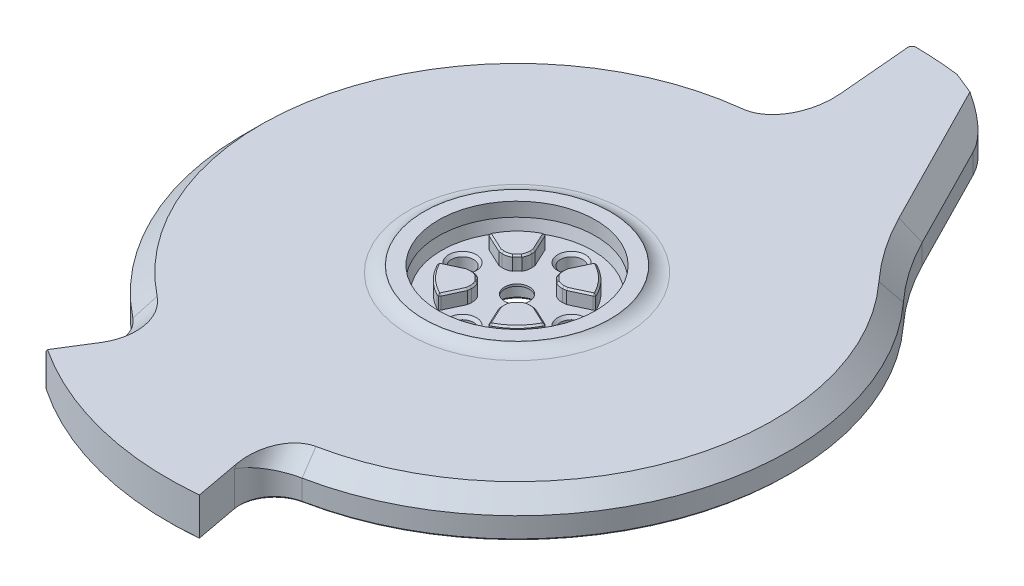
SolidWorks part; units mm, degrees
material "PLA/ABS"
ref_plane "Front Plane" through (0, 0, 0) normal (0, 0, 1) x (1, 0, 0)
ref_plane "Top Plane" through (0, 0, 0) normal (0, 1, 0) x (1, 0, 0)
ref_plane "Right Plane" through (0, 0, 0) normal (1, 0, 0) x (0, 0, -1)
other "Center of Mass"
other "Bounding Box"
ref_plane "Default Plane" through (-8.9266, -12.7485, 0) normal (-0.1736, 0.9848, 0) x (0.9848, 0.1736, 0)
sketch "Sketch1" plane through (0, 0, 0) normal (0, 1, 0) x (1, 0, 0)
  line L0 (0, 0.2571) -> (0, 50000.2571) construction
  line L1 (0, 72.39) -> (1.9477, 50.1272)
  line L2 (8.8732, 71.8441) -> (17.3326, 68.4263)
  line L3 (32.9034, 37.8667) -> (17.3326, 68.4263)
  line L4 (2.4773, 72.39) -> (50002.4773, 72.39) construction
  line L5 (5.6032, -58.1918) -> (-4782.8773, 49672.08) construction
  line L6 (6.2079, -64.4718) -> (3.5332, -50.0404)
  line L7 (-33.432, -53.5023) -> (-26.5834, -42.5423)
  line L8 (6.2079, -64.4718) -> (6.9383, -72.0567) construction
  line L9 (0, 72.39) -> (8.8732, 71.8441) construction
  circle A1 centre (0, 0) radius 72.39 construction
  arc A2 (1.9477, 50.1272) -> (-26.5834, -42.5423) centre (0, 0) ccw
  arc A3 (-33.432, -53.5023) -> (6.2079, -64.4718) centre (0.6999, -7.2689) ccw
  arc A4 (3.5332, -50.0404) -> (32.9034, 37.8667) centre (0, 0) ccw
  arc A5 (-33.432, -53.5023) -> (-4.8081, 49.9341) centre (0.6999, -7.2689) cw construction
  arc A6 (0, 72.39) -> (8.8732, 71.8441) centre (0, 0) cw
  dimension "D1" = 144.78
  dimension "D5" = 22.225
  dimension "D2" = 5
  dimension "D3" = 22
  dimension "D4" = 17.78
  dimension "D6" = 5
  dimension "D7" = 7.62
  dimension "D8" = 5.5
  dimension "D9" = 42.5
  dimension "D10" = 8.89
  dimension "D11" = 22
extrude "Boss-Extrude1" add sketch "Sketch1" along normal mid plane 7.239
fillet "Fillet6" radius 6.35 1 edges at (-26.5834, 0, 42.5423)
fillet "Fillet10" radius 50.8 1 edges at (32.9034, 0, -37.8667)
chamfer "Chamfer2" distance 3.175 angle 45 6 edges at (23.2738, 3.6195, -56.766) (46.5947, 3.6195, 18.5865) (-47.0376, 3.6195, -17.4354) (-31.5953, 3.6195, 50.5631) (-28.886, 3.6195, 43.1809) (32.7302, 3.6195, -39.2246)
fillet "Fillet1" radius 7.62 2 edges at (1.9477, -1.5875, -50.1272)
fillet "Fillet2" radius 6.35 2 edges at (3.5332, -1.5875, 50.0404)
fillet "Fillet5" radius 12.7 1 edges at (17.3326, -1.5875, -68.4263)
sketch "Sketch2" plane through (0, 3.6195, 0) normal (0, 1, 0) x (1, 0, 0)
  circle A0 centre (0, 0) radius 14.4145
  dimension "D1" = 28.829
extrude "Cut-Extrude1" cut sketch "Sketch2" against normal offset from surface (3.429 mm away) 3.81 up to face at (1.7804, -3.6195, -10.875)
sketch "Sketch3" plane through (0, 3.6195, 0) normal (0, 1, 0) x (1, 0, 0)
  circle A0 centre (0, 0) radius 14.4145 construction
  circle A1 centre (0, 0) radius 14.4145
  circle A2 centre (0, 0) radius 15.6845
  dimension "D1" = 1.27
extrude "Boss-Extrude2" add sketch "Sketch3" along normal offset from surface (1.143 mm away) 4.572 up to face at (0, 0.1905, -14.4145) offset beyond the face yes
sketch "Sketch12" plane through (0, 0.1905, 0) normal (0, 1, 0) x (1, 0, 0)
  line L0 (0, 0) -> (0, 10) construction
  line B0 (9.6843, -4.0405) -> (5.3677, -2.0277)
  line B1 (2.0277, -5.3677) -> (4.0405, -9.6843)
  line B2 (4.0405, 9.6843) -> (2.0277, 5.3677)
  line B3 (5.3677, 2.0277) -> (9.6843, 4.0405)
  line B4 (-9.6843, 4.0405) -> (-5.3677, 2.0277)
  line B5 (-2.0277, 5.3677) -> (-4.0405, 9.6843)
  line B6 (-4.0405, -9.6843) -> (-2.0277, -5.3677)
  line B7 (-5.3677, -2.0277) -> (-9.6843, -4.0405)
  arc B8 (11.3201, -1.3201) -> (8.6799, 1.3201) centre (10, 0) ccw
  arc B9 (8.6799, 1.3201) -> (11.3201, -1.3201) centre (10, 0) ccw
  arc B10 (3.3588, -3.3588) -> (4.0851, -2.4237) centre (0, 0) ccw
  arc B11 (5.3677, -2.0277) -> (4.0851, -2.4237) centre (4.9451, -2.934) ccw
  arc B12 (10.1437, -5.418) -> (9.6843, -4.0405) centre (9.2617, -4.9469) ccw
  arc B13 (8.1317, -8.1317) -> (10.1437, -5.418) centre (0, 0) ccw
  arc B14 (5.418, -10.1437) -> (8.1317, -8.1317) centre (0, 0) ccw
  arc B15 (2.4237, -4.0851) -> (2.0277, -5.3677) centre (2.934, -4.9451) ccw
  arc B16 (4.0851, 2.4237) -> (2.4237, 4.0851) centre (0, 0) ccw
  arc B17 (2.0277, 5.3677) -> (2.4237, 4.0851) centre (2.934, 4.9451) ccw
  arc B18 (10.1437, 5.418) -> (5.418, 10.1437) centre (0, 0) ccw
  arc B19 (9.9688, 4.2397) -> (10.1437, 5.418) centre (9.2617, 4.9469) ccw
  arc B20 (4.0851, 2.4237) -> (5.3677, 2.0277) centre (4.9451, 2.934) ccw
  arc B21 (-2.4237, 4.0851) -> (-4.0851, 2.4237) centre (0, 0) ccw
  arc B22 (-4.238, 2.2269) -> (-4.0851, 2.4237) centre (-4.9451, 2.934) ccw
  arc B23 (-5.3677, 2.0277) -> (-4.238, 2.2269) centre (-4.9451, 2.934) ccw
  arc B24 (-10.1437, 5.418) -> (-9.6843, 4.0405) centre (-9.2617, 4.9469) ccw
  arc B25 (-5.418, 10.1437) -> (-10.1437, 5.418) centre (0, 0) ccw
  arc B26 (-4.0405, 9.6843) -> (-5.418, 10.1437) centre (-4.9469, 9.2617) ccw
  arc B27 (-2.2269, 4.238) -> (-2.0277, 5.3677) centre (-2.934, 4.9451) ccw
  arc B28 (-2.4237, 4.0851) -> (-2.2269, 4.238) centre (-2.934, 4.9451) ccw
  arc B29 (1.4142, -1.4142) -> (-1.4142, 1.4142) centre (0, 0) ccw
  arc B30 (-1.4142, 1.4142) -> (1.4142, -1.4142) centre (0, 0) ccw
  arc B31 (-8.6799, -1.3201) -> (-11.3201, 1.3201) centre (-10, 0) ccw
  arc B32 (-11.3201, 1.3201) -> (-8.6799, -1.3201) centre (-10, 0) ccw
  arc B33 (-2.0277, -5.3677) -> (-2.4237, -4.0851) centre (-2.934, -4.9451) ccw
  arc B34 (-10.1437, -5.418) -> (-5.418, -10.1437) centre (0, 0) ccw
  arc B35 (-9.6843, -4.0405) -> (-10.1437, -5.418) centre (-9.2617, -4.9469) ccw
  arc B36 (-4.0851, -2.4237) -> (-5.3677, -2.0277) centre (-4.9451, -2.934) ccw
  arc B37 (1.3201, -11.3201) -> (-1.3201, -8.6799) centre (0, -10) ccw
  arc B38 (-1.3201, -8.6799) -> (1.3201, -11.3201) centre (0, -10) ccw
  arc B39 (1.3201, 8.6799) -> (-1.3201, 11.3201) centre (0, 10) ccw
  arc B40 (-1.3201, 11.3201) -> (1.3201, 8.6799) centre (0, 10) ccw
sketch_block_instance "Block-Repeat direct drive V2-1"
sketch_block "Block-Repeat direct drive V2"
sketch "Sketch13" plane through (0, 0.1905, 0) normal (0, 1, 0) x (1, 0, 0)
  arc B0 (3.2235, 3.3375) -> (-3.224, 3.337) centre (0, 0) ccw
  arc B1 (-3.224, 3.337) -> (-2.4077, 5.5782) centre (-5.4023, 5.3997) ccw
  arc B2 (-2.4077, 5.5782) -> (-3.1053, 9.1695) centre (-16.2471, 4.7532) ccw
  arc B3 (-3.1053, 9.1695) -> (-5.2201, 10.022) centre (-4.5272, 8.6917) ccw
  arc B4 (-10.0241, 5.2162) -> (-10.0214, -5.2213) centre (0, 0) ccw
  arc B5 (-10.0241, 5.2162) -> (-9.1709, 3.1018) centre (-8.6934, 4.5237) ccw
  arc B6 (-9.1709, 3.1018) -> (-5.5804, 2.405) centre (-4.7575, 16.2446) ccw
  arc B7 (-5.5804, 2.405) -> (-3.3386, 3.2224) centre (-5.4023, 5.3997) ccw
  arc B8 (-3.3386, 3.2224) -> (-3.2802, -3.2818) centre (0, 0) ccw
  arc B9 (-3.2802, -3.2818) -> (2.4823, -3.9202) centre (0, 0) ccw
  arc B10 (0, 14) -> (0, -14) centre (0, 0) ccw
  arc B11 (0, -14) -> (0, 14) centre (0, 0) ccw
sketch_block_instance "Block-Repeat direct drive V1-1"
sketch_block "Block-Repeat direct drive V1"
sketch "Sketch5" plane through (0, 0.1905, 0) normal (0, 1, 0) x (1, 0, 0)
  line L0 (-9.5072, 4.4204) -> (-6.1973, 2.877)
  line L1 (-2.8809, 6.2057) -> (-4.4204, 9.5072)
  line L6 (-2.0277, 5.3677) -> (-4.0405, 9.6843) construction
  line L7 (-9.6843, 4.0405) -> (-5.3677, 2.0277) construction
  line L8 (-2.472, 6.3205) -> (-4.0405, 9.6843) construction
  line L9 (-9.6843, 4.0405) -> (-6.3118, 2.4679) construction
  arc A0 (-3.224, 3.337) -> (-2.4077, 5.5782) centre (-5.4023, 5.3997) ccw construction
  arc A2 (-4.0405, 9.6843) -> (-5.418, 10.1437) centre (-4.9469, 9.2617) ccw construction
  arc A5 (-2.4077, 5.5782) -> (-3.1053, 9.1695) centre (-16.2471, 4.7532) ccw construction
  arc A10 (-10.1437, 5.418) -> (-9.6843, 4.0405) centre (-9.2617, 4.9469) ccw construction
  arc A13 (-2.4237, 4.0851) -> (-4.0851, 2.4237) centre (0, 0) ccw construction
  arc A14 (-4.0405, 9.6843) -> (-4.5771, 10.1908) centre (-4.9469, 9.2617) ccw construction
  arc A18 (-10.1923, 4.581) -> (-9.6843, 4.0405) centre (-9.2617, 4.9469) ccw construction
  arc A21 (-2.8778, 3.779) -> (-3.7804, 2.876) centre (0, 0) ccw construction
  arc A30 (-3.1053, 9.1695) -> (-5.2201, 10.022) centre (-4.5272, 8.6917) ccw construction
  arc A31 (-10.0241, 5.2162) -> (-9.1709, 3.1018) centre (-8.6934, 4.5237) ccw construction
  arc A32 (-9.1709, 3.1018) -> (-5.5804, 2.405) centre (-4.7575, 16.2446) ccw construction
  arc A33 (-5.5804, 2.405) -> (-3.3386, 3.2224) centre (-5.4023, 5.3997) ccw construction
  arc A34 (-2.8778, 3.779) -> (-2.4077, 5.5782) centre (-5.4023, 5.3997) ccw construction
  arc A35 (-2.4077, 5.5782) -> (-2.472, 6.3205) centre (-16.2471, 4.7532) ccw construction
  arc A36 (-4.5771, 10.1908) -> (-5.2201, 10.022) centre (-4.5272, 8.6917) ccw construction
  arc A37 (-10.0241, 5.2162) -> (-10.1923, 4.581) centre (-8.6934, 4.5237) ccw construction
  arc A38 (-6.3118, 2.4679) -> (-5.5804, 2.405) centre (-4.7575, 16.2446) ccw construction
  arc A39 (-5.5804, 2.405) -> (-3.7804, 2.876) centre (-5.4023, 5.3997) ccw construction
  arc A40 (-10.0241, 5.2162) -> (-5.2201, 10.022) centre (0, 0) cw construction
  arc A41 (-9.6523, 5.0227) -> (-9.7659, 4.6584) centre (-8.6934, 4.5237) ccw
  arc A42 (-9.7659, 4.6584) -> (-9.5072, 4.4204) centre (-9.2617, 4.9469) ccw
  arc A43 (-6.1973, 2.877) -> (-5.5555, 2.8233) centre (-4.7575, 16.2446) ccw
  arc A44 (-5.5555, 2.8233) -> (-4.0661, 3.1917) centre (-5.4023, 5.3997) ccw
  arc A45 (-3.1937, 4.0645) -> (-4.0661, 3.1917) centre (0, 0) ccw
  arc A46 (-3.1937, 4.0645) -> (-2.826, 5.5533) centre (-5.4023, 5.3997) ccw
  arc A47 (-2.826, 5.5533) -> (-2.8809, 6.2057) centre (-16.2471, 4.7532) ccw
  arc A48 (-4.4204, 9.5072) -> (-4.6565, 9.7648) centre (-4.9469, 9.2617) ccw
  arc A49 (-4.6565, 9.7648) -> (-5.0265, 9.6503) centre (-4.5272, 8.6917) ccw
  arc A50 (-9.6523, 5.0227) -> (-5.0265, 9.6503) centre (0, 0) cw
  dimension "D1" = 0.4191
extrude "Boss-Extrude3" add sketch "Sketch5" along normal blind 2.54
chamfer "Chamfer4" distance 0.3048 angle 45 12 edges at (-4.8467, 2.7305, -9.7243) (-4.5186, 2.7305, -9.6542) (-3.6506, 2.7305, -7.8564) (-2.8495, 2.7305, -5.8798) (-2.8967, 2.7305, -4.781) (-3.656, 2.7305, -3.6542) (-4.7828, 2.7305, -2.8943) (-5.8767, 2.7305, -2.8463) (-7.8522, 2.7305, -3.6487) (-9.655, 2.7305, -4.5194) (-9.7253, 2.7305, -4.8456) (-7.6955, 2.7305, -7.6924)
pattern_circular "CirPattern1" count 4 over 360 about axis through (0, 53.697, 0) along (0, -1, 0) of "Boss-Extrude3", "Chamfer4"
sketch "Sketch9" plane through (0, 0.1905, 0) normal (0, 1, 0) x (1, 0, 0)
  circle A3 centre (0, 0) radius 2.286
  circle A4 centre (-10, 0) radius 2.032
  circle A5 centre (0, 10) radius 2.032
  circle A6 centre (10, 0) radius 2.032
  circle A7 centre (0, -10) radius 2.032
  dimension "D1" = 4.064
  dimension "D2" = 4.572
extrude "Cut-Extrude4" cut sketch "Sketch9" against normal through all
chamfer "Chamfer1" distance 2.54 angle 45 1 edges at (0, 3.6195, -15.6845)
sketch "Sketch10" plane through (0, -3.6195, 0) normal (0, -1, 0) x (1, 0, 0)
  circle A0 centre (0, 10) radius 3.4925
  circle A1 centre (10, 0) radius 3.4925
  circle A2 centre (-10, 0) radius 3.4925
  circle A3 centre (0, -10) radius 3.4925
  dimension "D1" = 6.985
extrude "Cut-Extrude5" cut sketch "Sketch10" against normal blind 0.762
sketch "Sketch14" plane through (0, -3.6195, 0) normal (0, -1, 0) x (1, 0, 0)
  circle A0 centre (0, 0) radius 4
  dimension "D1" = 8
extrude "Cut-Extrude7" cut sketch "Sketch14" against normal offset from surface (2.8448 mm away) 0.9652 up to face at (-10, 0.1905, 2.032)
chamfer "Chamfer3" distance 1.016 angle 45 4 edges at (0, -3.6195, 6.5075) (-10, -3.6195, -3.4925) (10, -3.6195, -3.4925) (0, -3.6195, -13.4925)
fillet "Fillet7" radius 0.762 1 edges at (0, 0, -72.39)
fillet "Fillet8" radius 3.81 1 edges at (0, 3.6195, -18.2245)
chamfer "Chamfer5" distance 0.508 angle 45 8 edges at (0, -2.8575, 7.968) (-10, -2.8575, -2.032) (0, -2.8575, -12.032) (10, -2.8575, -2.032) (0, 0.1905, -7.968) (-10, 0.1905, 2.032) (0, 0.1905, 12.032) (10, 0.1905, 2.032)
fillet "Fillet9" radius 2.54 1 edges at (-33.432, -1.5875, 53.5023)
sketch "Sketch11" plane through (0, 4.7625, 0) normal (0, 1, 0) x (1, 0, 0)
  circle A0 centre (0, 0) radius 17.0815 construction
  circle A1 centre (0, 0) radius 17.0815
  circle A2 centre (0, 0) radius 74.3626
extrude "Cut-Extrude6" [suppressed] cut sketch "Sketch11" against normal through all
chamfer "Chamfer6" distance 2.032 angle 15 1 edges at (0, 0.1905, -14.4145) first distance on face at (0, 0.1905, -14.4145)
chamfer "Chamfer7" distance 0.381 angle 45 16 edges at (-13.4401, -3.6195, 62.9696) (-30.9592, -3.6195, 49.5451) (-28.886, -3.6195, 43.1809) (-48.2034, -3.6195, -13.8911) (-0.4484, -3.6195, -52.6045) (0.6615, -3.6195, -64.8285) (10.9016, -3.6195, -71.0246) (5.4778, -3.6195, 60.5324) (16.7525, -3.6195, -67.7933) (5.7358, -3.6195, 51.8719) (24.3516, -3.6195, -54.6506) (47.6665, -3.6195, 15.6342) (4.8646, -3.6195, -72.2264) (0.2732, -3.6195, -72.1412) (-32.4901, -3.6195, 53.3406) (32.7302, -3.6195, -39.2246)
chamfer "Chamfer9" distance 0.508 angle 45 1 edges at (0, -3.6195, -4)
chamfer "Chamfer11" distance 0.5842 angle 55 1 edges at (0, -0.7747, -2.286) first distance on face at (0, 0.1905, 2.286)
